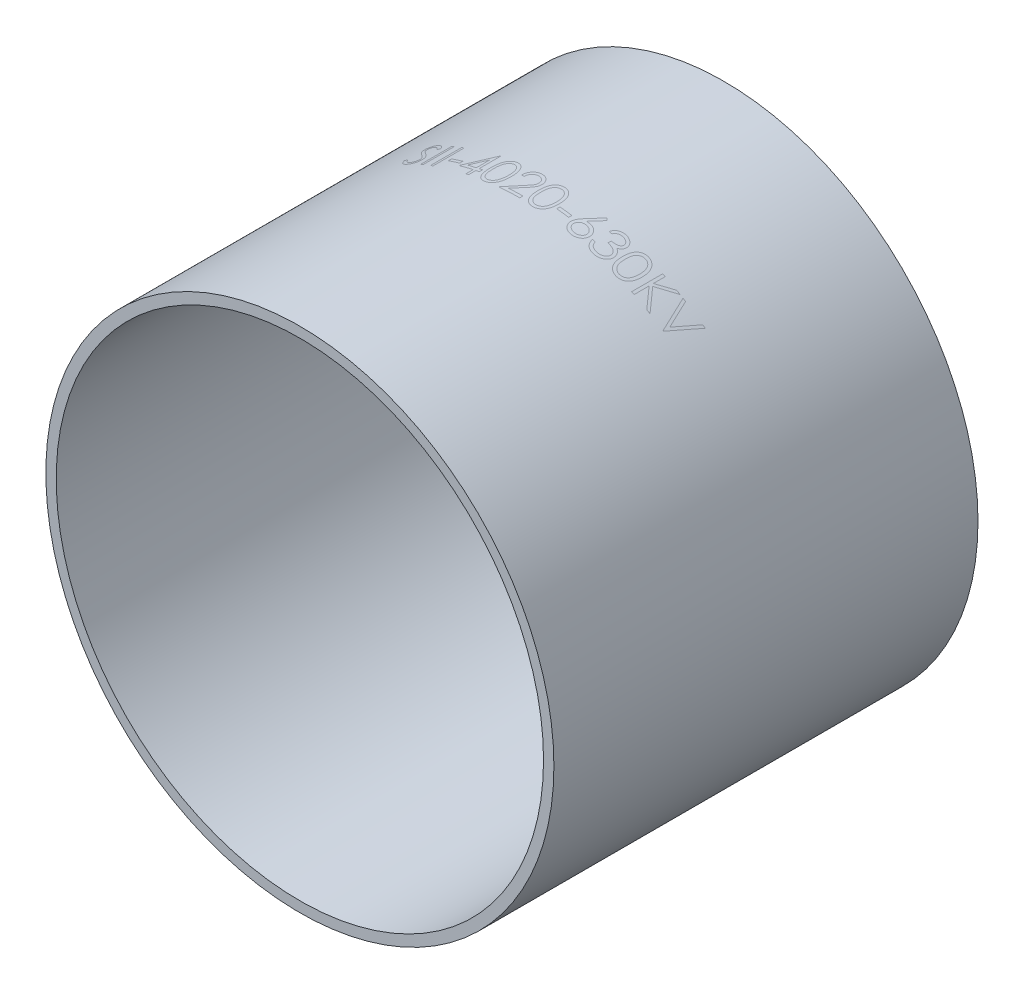
SolidWorks part; units mm, degrees
ref_plane "Plano frontal" through (0, 0, 0) normal (0, 0, 1) x (1, 0, 0)
ref_plane "Plano superior" through (0, 0, 0) normal (0, 1, 0) x (1, 0, 0)
ref_plane "Plano direito" through (0, 0, 0) normal (1, 0, 0) x (0, 0, -1)
sketch "Esboço1" plane through (0, 0, 0) normal (0, 0, 1) x (1, 0, 0)
  circle A0 centre (0, 0) radius 24.5
  circle A2 centre (0, 0) radius 23.5
  dimension "D1" = 49
  dimension "D2" = 47
extrude "Ressalto-extrusão1" add sketch "Esboço1" along normal blind 40.9
ref_plane "Plano1" through (0, 25, 0) normal (0, 1, 0) x (1, 0, 0)
sketch "Esboço2" plane through (0, 25, 0) normal (0, 1, 0) x (1, 0, 0)
  line L1 (9.8224, 22.0826) -> (5.4345, 29.9814) construction
  text T0 "SII-4020-630KV" font "Century Gothic" height 3
wrap "Envolver1" sketch "Esboço2" wrap type scribe source sketch "Esboço2" face at (24.5, 0, 40.9)
